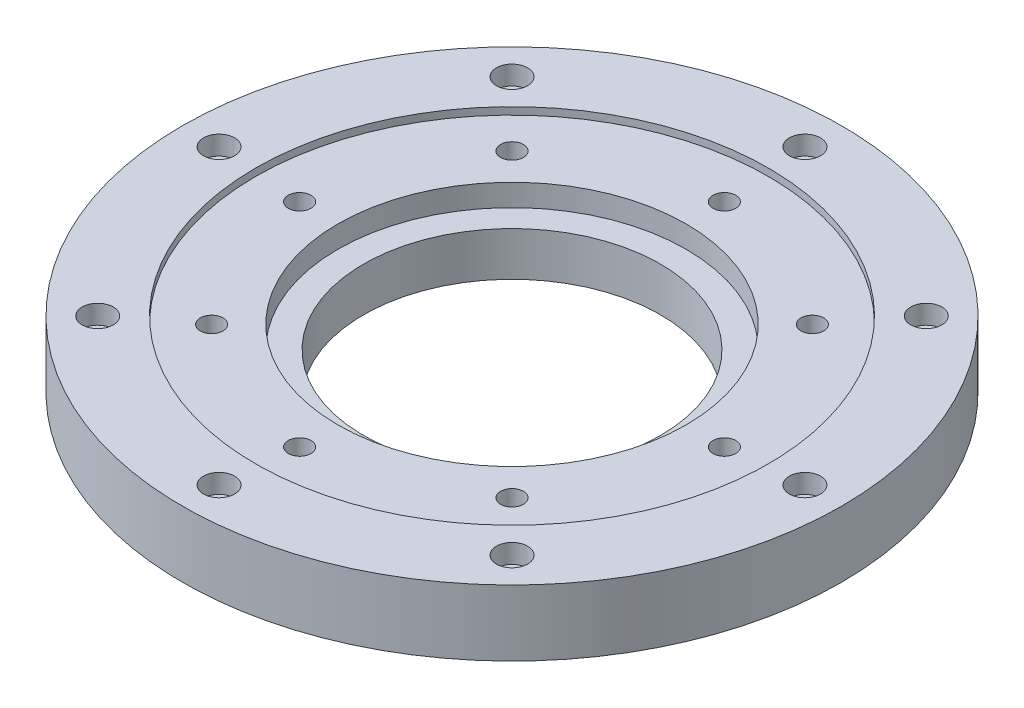
SolidWorks part; units mm, degrees
material "PVC rigide"
ref_plane "Plan de face" through (0, 0, 0) normal (0, 0, 1) x (1, 0, 0)
ref_plane "Plan de dessus" through (0, 0, 0) normal (0, 1, 0) x (1, 0, 0)
ref_plane "Plan de droite" through (0, 0, 0) normal (1, 0, 0) x (0, 0, -1)
sketch "Esquisse1" plane through (0, 0, 0) normal (0, 0, 1) x (1, 0, 0)
  line L0 (0, 0) -> (0, 73.3911) construction
  line L1 (-40.55, 0) -> (-40.55, 12)
  line L2 (-40.55, 12) -> (-47.55, 12)
  line L3 (-47.55, 12) -> (-47.55, 20)
  line L4 (-47.55, 20) -> (-65, 20)
  line L5 (-65, 2) -> (-65, 0)
  line L6 (-65, 0) -> (-50.3, 0)
  line L7 (-50.3, 0) -> (-50.3, 6)
  line L8 (-50.3, 6) -> (-47.1, 6)
  line L9 (-47.1, 6) -> (-47.1, 0)
  line L10 (-47.1, 0) -> (-40.55, 0)
  line L11 (-58, 20) -> (-58, 0) construction
  line L12 (-65, 2) -> (-90, 2)
  line L13 (-90, 2) -> (-90, 20)
  line L14 (-90, 20) -> (-65, 20)
  dimension "D1" = 7
  dimension "D2" = 95.1
  dimension "D3" = 6
  dimension "D4" = 20
  dimension "D5" = 6
  dimension "D6" = 58
  dimension "D7" = 94.2
  dimension "D8" = 100.6
  dimension "D9" = 130
  dimension "D10" = 90
  dimension "D11" = 2
revolve "Révolution1" add sketch "Esquisse1" angle 360 about L0
sketch "Esquisse2" plane through (0, 0, 0) normal (0, -1, 0) x (1, 0, 0)
  line L0 (0, 0) -> (0, 65) construction
  circle A0 centre (0, 0) radius 65 construction
  circle A1 centre (0, 58) radius 3.1
  circle A2 centre (41.0122, 41.0122) radius 3.1
  circle A3 centre (58, 0) radius 3.1
  circle A4 centre (41.0122, -41.0122) radius 3.1
  circle A5 centre (0, -58) radius 3.1
  circle A6 centre (-41.0122, -41.0122) radius 3.1
  circle A7 centre (-58, 0) radius 3.1
  circle A8 centre (-41.0122, 41.0122) radius 3.1
  dimension "D3" = 6.2
  dimension "D1" = 58
  dimension "D2" = 8
extrude "Enlèv. mat.-Extru.1" cut sketch "Esquisse2" against normal through all
sketch "Esquisse3" plane through (0, 20, 0) normal (0, 1, 0) x (1, 0, 0)
  circle A0 centre (0, 0) radius 70
  dimension "D1" = 140
extrude "Enlèv. mat.-Extru.2" cut sketch "Esquisse3" against normal blind 2
sketch "Esquisse4" plane through (0, 20, 0) normal (0, 1, 0) x (1, 0, 0)
  circle A0 centre (0, 0) radius 80 construction
  circle A1 centre (0, 80) radius 2.6
  circle A2 centre (56.5685, 56.5685) radius 2.6
  circle A3 centre (80, 0) radius 2.6
  circle A4 centre (56.5685, -56.5685) radius 2.6
  circle A5 centre (0, -80) radius 2.6
  circle A6 centre (-56.5685, -56.5685) radius 2.6
  circle A7 centre (-80, 0) radius 2.6
  circle A8 centre (-56.5685, 56.5685) radius 2.6
  dimension "D1" = 160
  dimension "D2" = 5.2
  dimension "D3" = 8
extrude "Enlèv. mat.-Extru.3" cut sketch "Esquisse4" against normal through all
sketch "Esquisse5" plane through (0, 20, 0) normal (0, 1, 0) x (1, 0, 0)
  circle A0 centre (0, 80) radius 4.25
  circle A1 centre (56.5685, 56.5685) radius 4.25
  circle A2 centre (80, 0) radius 4.25
  circle A3 centre (56.5685, -56.5685) radius 4.25
  circle A4 centre (0, -80) radius 4.25
  circle A5 centre (-56.5685, -56.5685) radius 4.25
  circle A6 centre (-80, 0) radius 4.25
  circle A7 centre (-56.5685, 56.5685) radius 4.25
  dimension "D1" = 8.5
  dimension "D2" = 8
extrude "Enlèv. mat.-Extru.4" cut sketch "Esquisse5" against normal blind 5.2
